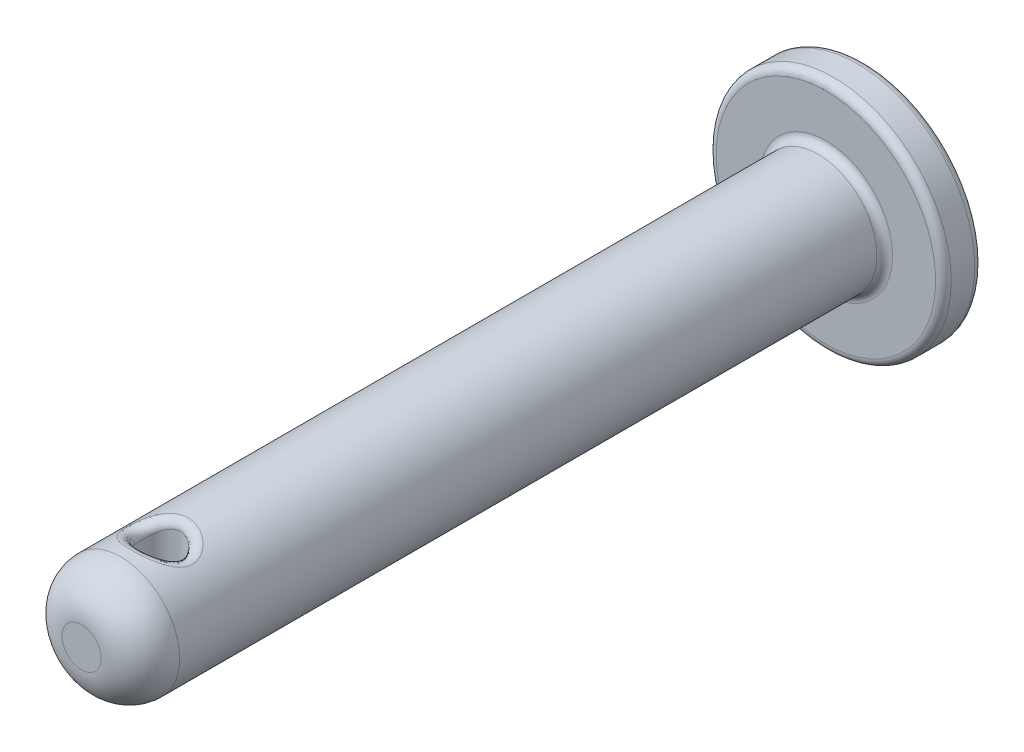
SolidWorks part; units mm, degrees
ref_plane "前基準面" through (0, 0, 0) normal (0, 0, 1) x (1, 0, 0)
ref_plane "上基準面" through (0, 0, 0) normal (0, 1, 0) x (1, 0, 0)
ref_plane "右基準面" through (0, 0, 0) normal (1, 0, 0) x (0, 0, -1)
sketch "草圖1" plane through (0, 0, 0) normal (0, 0, 1) x (1, 0, 0)
  circle A0 centre (0, 0) radius 7.5
  dimension "D1" = 15
extrude "填料-伸長1" add sketch "草圖1" along normal blind 100
fillet "圓角1" radius 5 1 edges at (7.5, 0, 100)
sketch "草圖2" plane through (0, 0, 0) normal (0, 1, 0) x (1, 0, 0)
  line L0 (-2.5, -100) -> (2.5, -100) construction
  line L1 (0, -100) -> (0, 0) construction
  circle A0 centre (0, -90) radius 2.6
  point P2 (0, 0)
  dimension "D2" = 5.2
  dimension "D1" = 10
extrude "除料-伸長1" cut sketch "草圖2" against normal through all and the other way through all
fillet "圓角2" radius 1 1 edges at (7.5, 0, 0)
fillet "圓角3" radius 1 2 edges at (-0.4297, -7.4877, 87.4357) (0.4297, 7.4877, 87.4357)
sketch "草圖3" plane through (0, 0, 0) normal (0, 1, 0) x (1, 0, 0)
  line L0 (0, -100) -> (0, 0) construction
  line L1 (-2.5, -100) -> (2.5, -100) construction
  line L2 (0, -5) -> (-15, -5)
  line L3 (-15, -5) -> (-15, 0)
  line L4 (-15, 0) -> (0, 0)
  line L5 (0, 0) -> (0, -5)
  line L6 (6.5, 0) -> (-6.5, 0) construction
  dimension "D1" = 5
  dimension "D2" = 5
  dimension "D3" = 15
revolve "旋轉1" add sketch "草圖3" angle 360 about L0
fillet "圓角4" radius 1 1 edges at (-7.5, 0, 5)
fillet "圓角5" radius 1 2 edges at (15, 0, 0) (15, 0, 5)
